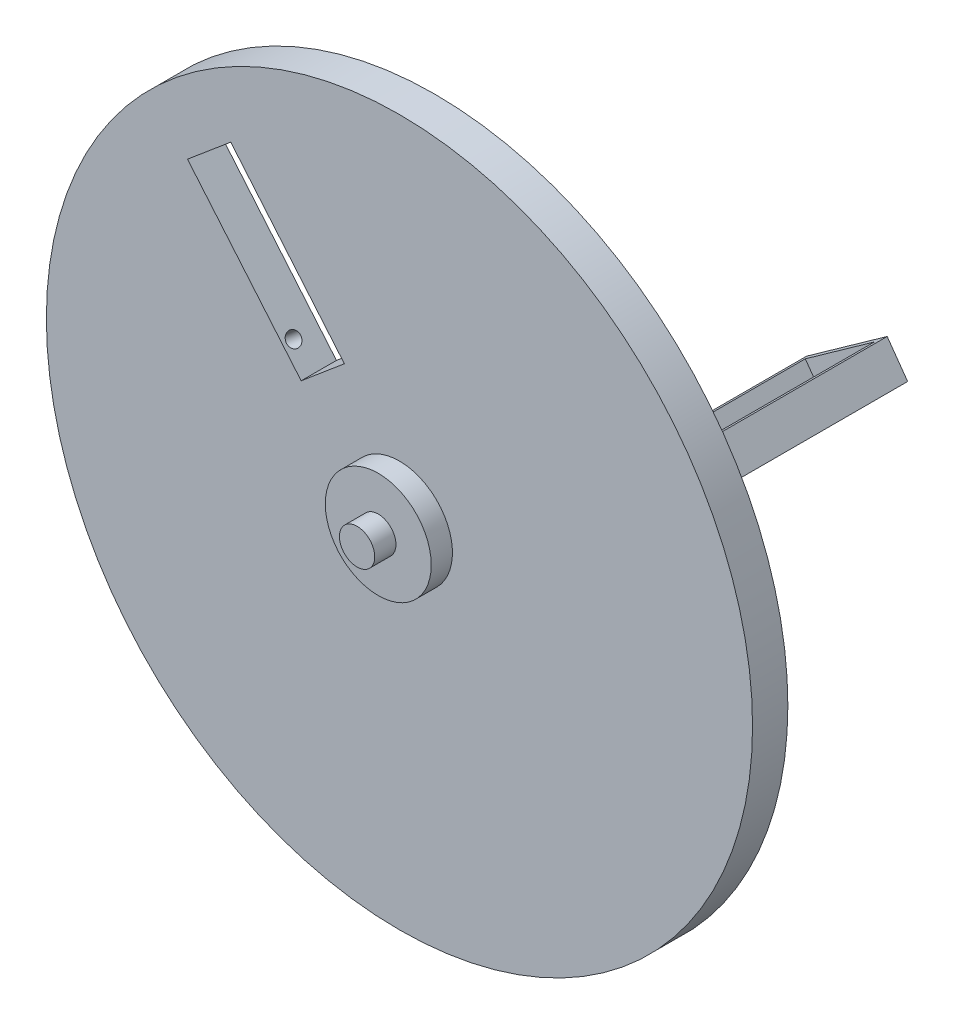
SolidWorks part; units mm, degrees
ref_plane "Front Plane" through (0, 0, 0) normal (0, 0, 1) x (1, 0, 0)
ref_plane "Top Plane" through (0, 0, 0) normal (0, 1, 0) x (1, 0, 0)
ref_plane "Right Plane" through (0, 0, 0) normal (1, 0, 0) x (0, 0, -1)
sketch "Sketch1" plane through (0, 0, 0) normal (0, 0, 1) x (1, 0, 0)
  line L1 (-50, -50) -> (50, -50)
  line L2 (-50, -50) -> (-50, 50)
  line L3 (-50, 50) -> (50, 50)
  line L4 (50, -50) -> (50, 50)
  line L5 (0, 50) -> (0, -50) construction
  line L6 (-50, 0) -> (50, 0) construction
  point P0 (0, 0)
  dimension "D1" = 100
  dimension "D2" = 100
extrude "Boss-Extrude1" add sketch "Sketch1" along normal blind 5
sketch "Sketch2" plane through (0, 0, 5) normal (0, 0, 1) x (1, 0, 0)
  circle A0 centre (0, 0) radius 7.5
  dimension "D1" = 15
extrude "Boss-Extrude2" add sketch "Sketch2" along normal blind 3
sketch "Sketch3" plane through (0, 0, 8) normal (0, 0, 1) x (1, 0, 0)
  circle A0 centre (0, 0) radius 2.5
  dimension "D1" = 5
extrude "Boss-Extrude3" add sketch "Sketch3" along normal blind 3
sketch "Sketch10" plane through (0, 0, 5) normal (0, 0, 1) x (1, 0, 0)
  line L0 (-13.9214, 10.3785) -> (-30.0142, 29.5102)
  line L1 (23.8921, -34.6599) -> (30.0557, -29.4753)
  line L2 (-30.0142, 29.5102) -> (-23.8921, 34.6599)
  line L3 (-7.7993, 15.5282) -> (-23.8921, 34.6599)
  line L4 (-23.8921, 34.6599) -> (-13.9214, 10.3785) construction
  line L5 (-30.0142, 29.5102) -> (-7.7993, 15.5282) construction
  line L6 (-7.7993, 15.5282) -> (-13.9214, 10.3785)
  line L7 (50, -50) -> (50, 50) construction
  point P1 (0, 0)
  point P3 (-18.9067, 22.5192)
  dimension "D1" = 25
  dimension "D2" = 8
  dimension "D3" = 29.4037
  dimension "D4" = 18.9067
  dimension "D5" = 19.9443
  dimension "D6" = 26.1079
  dimension "D7" = 57.7993
extrude "Cut-Extrude1" cut sketch "Sketch10" against normal through all contours L6 L3 L2 L0 region at (-18.9067, 22.5192, 5)
sketch "Sketch11" plane through (3.0818, 2.5923, 0) normal (-0.7653, -0.6437, 0) x (0, 0, 1)
  line L1 (0, 16.9037) -> (5, 16.9037) construction
  line L2 (5, 16.9037) -> (5, 41.9037) construction
  circle A0 centre (3.5, 20.9037) radius 1
  dimension "D1" = 2
  dimension "D2" = 4
  dimension "D3" = 1.5
extrude "Cut-Extrude2" cut sketch "Sketch11" against normal blind 5 and the other way blind 12
sketch "Sketch13" plane through (0, 0, 0) normal (0, 0, -1) x (-1, 0, 0)
  line L0 (-25.6533, 17.1898) -> (-37.0606, 25.3061)
  line L1 (-37.0606, 25.3061) -> (-39.9593, 21.2321)
  line L2 (-39.9593, 21.2321) -> (-28.552, 13.1158)
  line L3 (-28.552, 13.1158) -> (-25.6533, 17.1898)
  dimension "D1" = 5
  dimension "D2" = 14
extrude "Boss-Extrude5" add sketch "Sketch13" along normal blind 27
shell "Shell1" thickness 1 removed face at (34.2557, 17.1739, -13.5) removed face at (31.357, 21.2479, -13.5)
sketch "Sketch14" plane through (0, 0, 0) normal (0, 0, -1) x (-1, 0, 0)
  line L1 (-52.6661, -53.5195) -> (52.6661, -53.5195)
  line L2 (-52.6661, -53.5195) -> (-52.6661, 53.5195)
  line L3 (-52.6661, 53.5195) -> (52.6661, 53.5195)
  line L4 (52.6661, -53.5195) -> (52.6661, 53.5195)
  line L5 (0, 53.5195) -> (0, -53.5195) construction
  line L6 (-52.6661, 0) -> (52.6661, 0) construction
  circle A0 centre (0, 0) radius 50
extrude "Cut-Extrude3" cut sketch "Sketch14" against normal through all
sketch "Sketch15" plane through (0, 0, 5) normal (0, 0, 1) x (1, 0, 0)
  circle A0 centre (0, 0) radius 50
  circle A1 centre (0, 0) radius 48.2018
extrude "Boss-Extrude6" add sketch "Sketch15" against normal up to surface (5 mm away) up to face at (-18.9067, 22.5192, 0)
sketch "Sketch16" plane through (0, 0, 0) normal (0, 0, -1) x (-1, 0, 0)
  line L1 (26, 5) -> (24, 5)
  line L2 (26, 5) -> (26, -5)
  line L3 (26, -5) -> (24, -5)
  line L4 (24, 5) -> (24, -5)
  line L5 (25, -5) -> (25, 5) construction
  line L6 (26, 0) -> (24, 0) construction
  point P0 (25, 0)
  point P4 (0, 0)
  dimension "D1" = 2
  dimension "D2" = 10
  dimension "D3" = 25
extrude "Boss-Extrude7" add sketch "Sketch16" along normal blind 2
